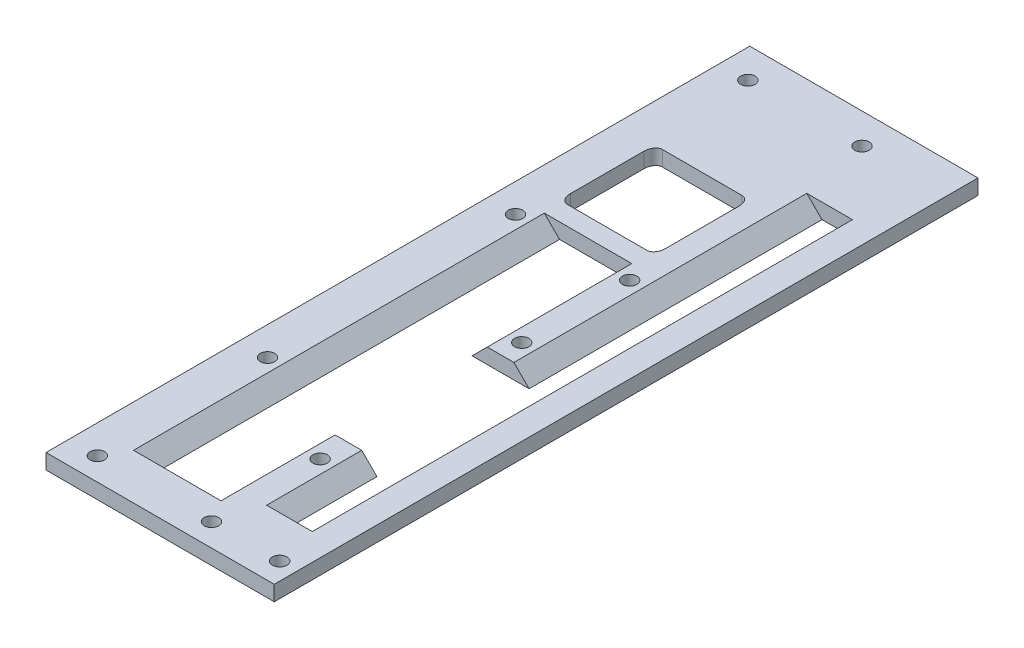
SolidWorks part; units mm, degrees
ref_plane "Płaszczyzna przednia" through (0, 0, 0) normal (0, 0, 1) x (1, 0, 0)
ref_plane "Płaszczyzna górna" through (0, 0, 0) normal (0, 1, 0) x (1, 0, 0)
ref_plane "Płaszczyzna prawa" through (0, 0, 0) normal (1, 0, 0) x (0, 0, -1)
sketch "Szkic1" plane through (0, 0, 0) normal (0, 0, 1) x (1, 0, 0)
  line L0 (-11.5, 2) -> (-7.5, -2)
  line L1 (-22.5, 2) -> (22.5, 2)
  line L2 (-22.5, 2) -> (-22.5, -2)
  line L3 (-22.5, -2) -> (22.5, -2)
  line L4 (22.5, 2) -> (22.5, -2)
  line L5 (-22.5, 2) -> (22.5, -2) construction
  line L6 (-22.5, -2) -> (22.5, 2) construction
  line L7 (0, 0) -> (0, 4.7316) construction
  line L8 (11.5, 2) -> (7.5, -2)
  point P0 (0, 0)
  dimension "D1" = 4
  dimension "D2" = 45
  dimension "D3" = 15
  dimension "D4" = 45
extrude "Dodanie-wyciągnięcie1" add sketch "Szkic1" against normal blind 110 contours L2 L3 L0 L1 | L1 L8 L3 L4 region at (-15.9487, -0.1026, 0) region at (15.9487, -0.1026, 0)
sketch "Szkic2" plane through (0, -2, 0) normal (0, -1, 0) x (1, 0, 0)
  line L0 (22.5, -110) -> (22.5, 0) construction
  line L1 (-22.5, 0) -> (22.5, 0)
  line L2 (-22.5, 0) -> (-22.5, 5)
  line L3 (-22.5, 5) -> (22.5, 5)
  line L4 (22.5, 0) -> (22.5, 5)
  line L6 (-22.5, -110) -> (22.5, -110)
  line L7 (-22.5, -110) -> (-22.5, -115)
  line L8 (-22.5, -115) -> (22.5, -115)
  line L9 (22.5, -110) -> (22.5, -115)
  dimension "D1" = 5
  dimension "D2" = 5
extrude "Dodanie-wyciągnięcie2" add sketch "Szkic2" against normal up to vertex (4 mm away) up to point (22.5, 2, -110)
sketch "Szkic4" plane through (0, 2, 0) normal (0, 1, 0) x (1, 0, 0)
  line L0 (-22.5, 55) -> (22.5, 55) construction
  line L1 (-22.5, 115) -> (-22.5, -5) construction
  line L2 (22.5, 115) -> (22.5, -5) construction
  line L4 (5, 70) -> (40, 70)
  line L5 (5, 70) -> (5, 40)
  line L6 (5, 40) -> (40, 40)
  line L7 (40, 70) -> (40, 40)
  line L8 (5, 70) -> (40, 40) construction
  line L9 (5, 40) -> (40, 70) construction
  dimension "D1" = 30
  dimension "D2" = 35
extrude "Wytnij-wyciągnięcie1" cut sketch "Szkic4" against normal blind 10
sketch "Szkic5" plane through (0, -2, 0) normal (0, -1, 0) x (1, 0, 0)
  line L0 (-22.5, -115) -> (22.5, -115) construction
  line L1 (22.5, 5) -> (37.5, 5)
  line L2 (22.5, 5) -> (22.5, -175)
  line L3 (22.5, -175) -> (37.5, -175)
  line L4 (37.5, 5) -> (37.5, -175)
  line L6 (22.5, -175) -> (-22.5, -175)
  line L7 (22.5, -175) -> (22.5, -115)
  line L8 (22.5, -115) -> (-22.5, -115)
  line L9 (-22.5, -175) -> (-22.5, -115)
  line M10 (22.5, -40) -> (22.5, 5)
  line M13 (-22.5, -115) -> (22.5, -115)
  line M14 (22.5, -115) -> (22.5, -70)
  dimension "D1" = 15
  dimension "D2" = 60
extrude "Dodanie-wyciągnięcie3" add sketch "Szkic5" against normal up to vertex (4 mm away) contours L9 L6 L2 M13 | L4 L1 L2 L3 M10 M14 region at (30, -2, -85) region at (0, -2, -145) up to point (-22.5, 2, -115)
sketch "Szkic6" plane through (0, 2, 0) normal (0, 1, 0) x (1, 0, 0)
  line L0 (37.5, -5) -> (37.5, 175) construction
  line L1 (22.5, 155) -> (26.5, 155)
  line L2 (22.5, 155) -> (22.5, 7)
  line L3 (22.5, 7) -> (26.5, 7)
  line L4 (26.5, 155) -> (26.5, 7)
  line L5 (37.5, -5) -> (-22.5, -5) construction
  line L6 (11.5, 110) -> (-11.5, 110) construction
  dimension "D1" = 15
  dimension "D2" = 4
  dimension "D3" = 12
  dimension "D4" = 45
extrude "Wytnij-wyciągnięcie2" cut sketch "Szkic6" against normal blind 10
chamfer "Sfazowanie1" distance 4 angle 45 3 edges at (22.5, 2, -23.5) (22.5, 2, -112.5) (26.5, 2, -81)
sketch "Szkic7" plane through (0, 0, 0) normal (0, 0, -1) x (-1, 0, 0)
  line L4 (-11.5, 2) -> (-7.5, -2)
  line L5 (-7.5, -2) -> (7.5, -2)
  line L6 (7.5, -2) -> (11.5, 2)
  line L7 (11.5, 2) -> (-11.5, 2)
  line L8 (-11.5, 2) -> (-7.5, -2)
  line L9 (-7.5, -2) -> (7.5, -2)
  line L10 (7.5, -2) -> (11.5, 2)
  line L11 (11.5, 2) -> (-11.5, 2)
  dimension "D1" = 0
extrude "Dodanie-wyciągnięcie4" add sketch "Szkic7" along normal blind 2
sketch "Szkic9" plane through (0, -2, 0) normal (0, -1, 0) x (1, 0, 0)
  line L0 (7.5, -40) -> (7.5, -2) construction
  line L1 (7.5, -32) -> (22.5, -32)
  line L2 (7.5, -32) -> (7.5, -72)
  line L3 (7.5, -72) -> (22.5, -72)
  line L4 (22.5, -32) -> (22.5, -72)
  line L5 (22.5, -70) -> (22.5, -155) construction
  line L7 (7.5, -2) -> (-7.5, -2) construction
  dimension "D1" = 30
  dimension "D2" = 40
extrude "Wytnij-wyciągnięcie3" cut sketch "Szkic9" against normal blind 80 contours L2 L1 L4 L3
sketch "Szkic10" plane through (0, 0, -155) normal (0, 0, 1) x (1, 0, 0)
  line L4 (22.5, -2) -> (26.5, -2)
  line L5 (26.5, -2) -> (30.5, 2)
  line L6 (30.5, 2) -> (18.5, 2)
  line L7 (18.5, 2) -> (22.5, -2)
  line L8 (22.5, -2) -> (26.5, -2)
  line L9 (26.5, -2) -> (30.5, 2)
  line L10 (30.5, 2) -> (18.5, 2)
  line L11 (18.5, 2) -> (22.5, -2)
  dimension "D1" = 0
extrude "Dodanie-wyciągnięcie5" add sketch "Szkic10" along normal blind 6
sketch "Szkic12" plane through (0, 2, 0) normal (0, 1, 0) x (1, 0, 0)
  line L12 (12.5, 117.8284) -> (12.5, 137.1716)
  line L13 (-10.5, 115) -> (10.5, 115)
  line L14 (-12.5, 137.1716) -> (-12.5, 117.8284)
  line L15 (10.5, 140) -> (-10.5, 140)
  ellipse E4 centre (10.5, 117.8284) end of major axis (10.5, 115) minor radius 2 (10.5, 115) -> (12.5, 117.8284) ccw
  ellipse E5 centre (-10.5, 117.8284) end of major axis (-10.5, 115) minor radius 2 (-12.5, 117.8284) -> (-10.5, 115) ccw
  ellipse E6 centre (-10.5, 137.1716) end of major axis (-10.5, 134.3431) minor radius 2 (-10.5, 140) -> (-12.5, 137.1716) ccw
  ellipse E7 centre (10.5, 137.1716) end of major axis (10.5, 134.3431) minor radius 2 (12.5, 137.1716) -> (10.5, 140) ccw
extrude "Wytnij-wyciągnięcie4" cut sketch "Szkic12" against normal blind 6
sketch "Szkic13" plane through (0, -2, 0) normal (0, -1, 0) x (1, 0, 0)
  line L0 (-22.5, -175) -> (-22.5, 5) construction
  line L1 (-22.5, 5) -> (37.5, 5)
  line L2 (-22.5, 5) -> (-22.5, 10)
  line L3 (-22.5, 10) -> (37.5, 10)
  line L4 (37.5, 5) -> (37.5, 10)
  line L5 (37.5, 5) -> (-22.5, 5) construction
  point P8 (37.5, 5)
  dimension "D1" = 5
extrude "Dodanie-wyciągnięcie6" add sketch "Szkic13" against normal blind 4
sketch "Szkic14" plane through (0, -2, 0) normal (0, -1, 0) x (1, 0, 0)
  line L0 (15, -72) -> (15, -175) construction
  line L1 (7.5, -72) -> (22.5, -72) construction
  line L2 (37.5, -175) -> (-22.5, -175) construction
  line L3 (15, -32) -> (15, 10) construction
  line L4 (7.5, -32) -> (22.5, -32) construction
  line L5 (37.5, 10) -> (-22.5, 10) construction
  line L6 (0, -2) -> (0, 10) construction
  line L7 (7.5, -2) -> (-7.5, -2) construction
  line L8 (-7.5, -2) -> (-22.5, -2) construction
  line L9 (-22.5, -175) -> (-22.5, 10) construction
  line L10 (-15, -2) -> (-15, -175) construction
  line L11 (0, 4) -> (-22.5, 4) construction
  line L12 (-15, -2) -> (-15, 10) construction
  line L13 (0, 4) -> (37.5, 4) construction
  line L14 (37.5, 10) -> (37.5, -175) construction
  line L15 (37.5, -167) -> (-22.5, -167) construction
  point P31 (-15, -167)
  point P33 (15, -167)
  point P35 (-15, 4)
  point P37 (15, 4)
  point P39 (32.9334, 4)
  point P41 (-15, -105.9207)
  point P43 (-15, -40.7239)
  point P45 (15, -24.5572)
  point P47 (15, -77.5628)
  point P49 (15, -105.9207)
  dimension "D1" = 8
hole_wizard "Otwory ustalające Ø3.0mm1" positions "Szkic14" profile "Szkic15" hole size "Ø3.0" standard "DIN" end condition through all
sketch "Szkic15" plane through (15, -2, -105.9207) normal (1, 0, 0) x (0, 0, -1)
  line L0 (0, 0) -> (0, 4)
  line L1 (0, 4) -> (1.9, 4)
  line L2 (1.9, 4) -> (1.9, 0)
  line L5 (1.9, 0) -> (0, 0)
  line L11 (0, -6.35) -> (0, 107.95) construction
  dimension "Średnica otworu na wylot" = 3.8
  dimension "Głębokość otworu na wylot" = 4
